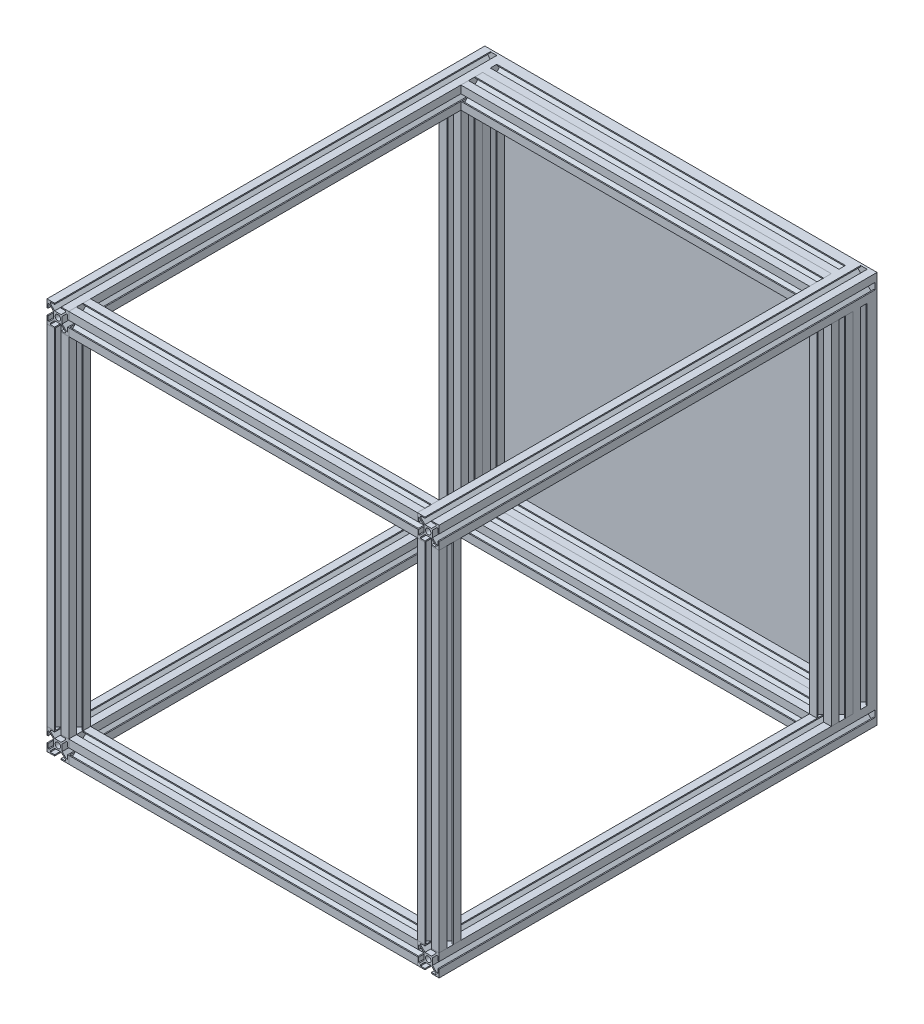
SolidWorks part; units mm, degrees
material "6063-T1"
ref_plane "Front Plane" through (0, 0, 0) normal (1, 0, 0) x (0, 1, 0)
ref_plane "Top Plane" through (0, 0, 0) normal (0, 0, 1) x (0, 1, 0)
ref_plane "Right Plane" through (0, 0, 0) normal (0, 1, 0) x (-1, 0, 0)
ref_axis "Axis1" through (0, 0, 0) along (0, 0, 1)
sketch "Sketch2" plane through (0, 0, 0) normal (1, 0, 0) x (0, 1, 0)
  line L5 (-180, 3) -> (-180, 10)
  line L67 (-180, 10) -> (-160, 10) construction
  line L68 (-180, 10) -> (-180, -10) construction
  line L69 (-180, -10) -> (-160, -10) construction
  line L70 (-160, 10) -> (-160, -10) construction
  line L72 (-160, 0) -> (160, 0) construction
  line L73 (-180, 10) -> (-173, 10)
  line L74 (-173, 10) -> (-173, 9)
  line L75 (-173, 9) -> (-177, 9)
  line L76 (-177, 9) -> (-177, 7.9857)
  line L77 (-177, 7.9857) -> (-173, 3.9857)
  line L78 (-173, 3.9857) -> (-170, 3.9857)
  line L79 (-180, 3) -> (-179, 3)
  line L80 (-179, 3) -> (-179, 7)
  line L81 (-179, 7) -> (-177.9857, 7)
  line L82 (-177.9857, 7) -> (-173.9857, 3)
  line L83 (-173.9857, 3) -> (-173.9857, 0)
  line L84 (-173.9857, 3) -> (-173, 3.9857) construction
  line L85 (-167, 10) -> (-160, 10)
  line L86 (-160, 10) -> (-160, 3)
  line L87 (-160, 3) -> (-161, 3)
  line L88 (-161, 3) -> (-161, 7)
  line L89 (-161, 7) -> (-162.0143, 7)
  line L90 (-162.0143, 7) -> (-166.0143, 3)
  line L91 (-166.0143, 3) -> (-166.0143, 0)
  line L92 (-167, 10) -> (-167, 9)
  line L93 (-167, 9) -> (-163, 9)
  line L94 (-163, 9) -> (-163, 7.9857)
  line L95 (-163, 7.9857) -> (-167, 3.9857)
  line L96 (-167, 3.9857) -> (-170, 3.9857)
  line L97 (-167, 3.9857) -> (-166.0143, 3) construction
  line L98 (-160, -3) -> (-160, -10)
  line L99 (-160, -10) -> (-167, -10)
  line L100 (-167, -10) -> (-167, -9)
  line L101 (-167, -9) -> (-163, -9)
  line L102 (-163, -9) -> (-163, -7.9857)
  line L103 (-163, -7.9857) -> (-167, -3.9857)
  line L104 (-167, -3.9857) -> (-170, -3.9857)
  line L105 (-160, -3) -> (-161, -3)
  line L106 (-161, -3) -> (-161, -7)
  line L107 (-161, -7) -> (-162.0143, -7)
  line L108 (-162.0143, -7) -> (-166.0143, -3)
  line L109 (-166.0143, -3) -> (-166.0143, 0)
  line L110 (-166.0143, -3) -> (-167, -3.9857) construction
  line L111 (-173, -10) -> (-180, -10)
  line L112 (-180, -10) -> (-180, -3)
  line L113 (-180, -3) -> (-179, -3)
  line L114 (-179, -3) -> (-179, -7)
  line L115 (-179, -7) -> (-177.9857, -7)
  line L116 (-177.9857, -7) -> (-173.9857, -3)
  line L117 (-173.9857, -3) -> (-173.9857, 0)
  line L118 (-173, -10) -> (-173, -9)
  line L119 (-173, -9) -> (-177, -9)
  line L120 (-177, -9) -> (-177, -7.9857)
  line L121 (-177, -7.9857) -> (-173, -3.9857)
  line L122 (-173, -3.9857) -> (-170, -3.9857)
  line L123 (-173, -3.9857) -> (-173.9857, -3) construction
  circle A0 centre (-170, 0) radius 2.5
  point P0 (-192.5803, 22.4509)
  point P6 (0, 0)
  point P9 (0, 0)
  point P10 (-162.6206, -0.6265)
  point P33 (-162.5743, -0.6264)
  point P46 (-173.9654, 0.3965)
  point P55 (-160, 0)
  point P72 (-160, 0)
  point P107 (-170, 0)
  dimension "D5" = 5
  dimension "D1" = 20
  dimension "D2" = 45
  dimension "D4" = 6
  dimension "D3" = 14
  dimension "D8" = 45
  dimension "D7" = 1
  dimension "D6" = 4
sketch "Sketch1" plane through (0, 0, 0) normal (0, 0, 1) x (0, 1, 0)
  line L0 (-160, 160) -> (160, -160) construction
  line L5 (-160, 160) -> (160, 160)
  line L6 (-160, 160) -> (-160, -160)
  line L7 (-160, -160) -> (160, -160)
  line L8 (160, 160) -> (160, -160)
  point P108 (0, 0)
  dimension "D1" = 320
  dimension "D2" = 320
sweep "Aluminium Extrsion Base" add profiles "Sketch2" path "Sketch1"
pattern_circular "CirPattern1" count 4 over 360 about axis through (0, 0, 0) along (0, 0, 1) of "Aluminium Extrsion Base"
mirror "Mirror5" about plane through (-160, 167, 10) normal (0, 0, -1) of bodies 122 118 124 123
sketch "Sketch4" plane through (0, 0, -10) normal (0, 0, 1) x (0, 1, 0)
  line L5 (-180, -167) -> (-180, -160)
  line L67 (-180, -160) -> (-160, -160) construction
  line L68 (-180, -160) -> (-180, -180) construction
  line L69 (-180, -180) -> (-160, -180) construction
  line L70 (-160, -160) -> (-160, -180) construction
  line L71 (-160, -167) -> (-160, -170) construction
  line L73 (-180, -160) -> (-173, -160)
  line L74 (-173, -160) -> (-173, -161)
  line L75 (-173, -161) -> (-177, -161)
  line L76 (-177, -161) -> (-177, -162.0896)
  line L77 (-177, -162.0896) -> (-173, -166.0896)
  line L78 (-173, -166.0896) -> (-170, -166.0896)
  line L79 (-180, -167) -> (-179, -167)
  line L80 (-179, -167) -> (-179, -163)
  line L81 (-179, -163) -> (-177.9104, -163)
  line L82 (-177.9104, -163) -> (-173.9104, -167)
  line L83 (-173.9104, -167) -> (-173.9104, -170)
  line L84 (-173.9104, -167) -> (-173, -166.0896) construction
  line L85 (-167, -160) -> (-160, -160)
  line L86 (-160, -160) -> (-160, -167)
  line L87 (-160, -167) -> (-161, -167)
  line L88 (-161, -167) -> (-161, -163)
  line L89 (-161, -163) -> (-162.0896, -163)
  line L90 (-162.0896, -163) -> (-166.0896, -167)
  line L91 (-166.0896, -167) -> (-166.0896, -170)
  line L92 (-167, -160) -> (-167, -161)
  line L93 (-167, -161) -> (-163, -161)
  line L94 (-163, -161) -> (-163, -162.0896)
  line L95 (-163, -162.0896) -> (-167, -166.0896)
  line L96 (-167, -166.0896) -> (-170, -166.0896)
  line L97 (-167, -166.0896) -> (-166.0896, -167) construction
  line L98 (-160, -173) -> (-160, -180)
  line L99 (-160, -180) -> (-167, -180)
  line L100 (-167, -180) -> (-167, -179)
  line L101 (-167, -179) -> (-163, -179)
  line L102 (-163, -179) -> (-163, -177.9104)
  line L103 (-163, -177.9104) -> (-167, -173.9104)
  line L104 (-167, -173.9104) -> (-170, -173.9104)
  line L105 (-160, -173) -> (-161, -173)
  line L106 (-161, -173) -> (-161, -177)
  line L107 (-161, -177) -> (-162.0896, -177)
  line L108 (-162.0896, -177) -> (-166.0896, -173)
  line L109 (-166.0896, -173) -> (-166.0896, -170)
  line L110 (-166.0896, -173) -> (-167, -173.9104) construction
  line L111 (-173, -180) -> (-180, -180)
  line L112 (-180, -180) -> (-180, -173)
  line L113 (-180, -173) -> (-179, -173)
  line L114 (-179, -173) -> (-179, -177)
  line L115 (-179, -177) -> (-177.9104, -177)
  line L116 (-177.9104, -177) -> (-173.9104, -173)
  line L117 (-173.9104, -173) -> (-173.9104, -170)
  line L118 (-173, -180) -> (-173, -179)
  line L119 (-173, -179) -> (-177, -179)
  line L120 (-177, -179) -> (-177, -177.9104)
  line L121 (-177, -177.9104) -> (-173, -173.9104)
  line L122 (-173, -173.9104) -> (-170, -173.9104)
  line L123 (-173, -173.9104) -> (-173.9104, -173) construction
  line L124 (-167, -160) -> (-170, -160) construction
  circle A0 centre (-170, -170) radius 2.5
  point P0 (-192.5803, 22.4509)
  point P6 (0, 0)
  point P9 (0, 0)
  point P10 (-162.6206, -0.6265)
  point P33 (-162.5743, -0.6264)
  point P46 (-173.9654, 0.3965)
  point P55 (-160, 0)
  point P59 (-170.799, -170.6795)
  point P72 (-160, -170)
  point P107 (-170, -170)
  dimension "D2" = 45
  dimension "D5" = 5
  dimension "D1" = 20
  dimension "D3" = 14
  dimension "D4" = 6
  dimension "D7" = 1
  dimension "D8" = 45
  dimension "D6" = 4
extrude "Aluminium Extrusion Pillar" add sketch "Sketch4" along normal blind 400 separate body
pattern_circular "CirPattern2" count 4 over 360 about axis through (0, 0, 0) along (0, 0, 1) of bodies 125
ref_plane "Plane2" through (0, 0, 190) normal (0, 0, 1) x (1, 0, 0)
mirror "Mirror4" about plane through (0, 0, 190) normal (0, 0, 1) of bodies 124 118 122 123
sketch "Sketch5" plane through (0, 0, -10) normal (0, 0, -1) x (1, 0, 0)
  line L1 (-180, 180) -> (180, 180)
  line L2 (-180, 180) -> (-180, -180)
  line L3 (-180, -180) -> (180, -180)
  line L4 (180, 180) -> (180, -180)
  line L5 (0, -180) -> (0, 180) construction
  line L6 (-180, 0) -> (180, 0) construction
  circle A0 centre (-170, -170) radius 2.5 construction
  circle A1 centre (170, -170) radius 2.5 construction
  circle A2 centre (170, 170) radius 2.5 construction
  circle A3 centre (-170, 170) radius 2.5 construction
  circle A4 centre (-170, -170) radius 2.5
  circle A5 centre (170, -170) radius 2.5
  circle A6 centre (170, 170) radius 2.5
  circle A7 centre (-170, 170) radius 2.5
  point P308 (0, 0)
extrude "Boss-Extrude9" add sketch "Sketch5" along normal blind 2
equation "\"extrusion_width\"= 20mm"
equation "\"frame_height\"= 360mm"
equation "\"frame_width\"= 320mm"
equation "\"frame_length\"= 320mm"
equation "\"bed_radius\"= 200mm"
equation "\"bottom_plate_thickness\"=2"
equation "\"D2@Sketch1\"=\"frame_length\""
equation "\"D1@Sketch1\"=\"frame_width\""
equation "\"D1@Sketch2\"=\"extrusion_width\""
equation "\"D1@Aluminium Extrusion Pillar\" = \"frame_height\" + \"extrusion_width\" * 2"
equation "\"D1@Boss-Extrude9\"=\"bottom_plate_thickness\""
